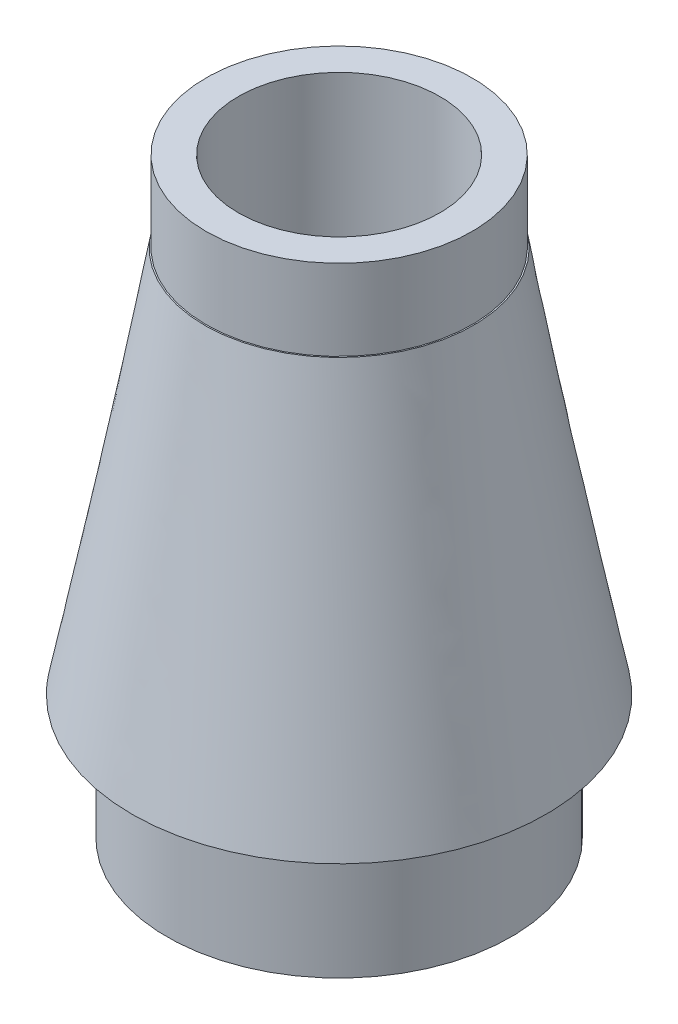
SolidWorks part; units mm, degrees
ref_plane "Front Plane" through (0, 0, 0) normal (0, 0, 1) x (1, 0, 0)
ref_plane "Top Plane" through (0, 0, 0) normal (0, 1, 0) x (1, 0, 0)
ref_plane "Right Plane" through (0, 0, 0) normal (1, 0, 0) x (0, 0, -1)
sketch "Sketch1" plane through (0, 0, 0) normal (0, 1, 0) x (1, 0, 0)
  circle A0 centre (0, 0) radius 3.2
  dimension "D1" = 6.4
ref_plane "Plane1" through (0, 2.3, 0) normal (0, 1, 0) x (-1, 0, 0)
sketch "Sketch2" plane through (0, 2.3, 0) normal (0, 1, 0) x (-1, 0, 0)
  circle A0 centre (0, 0) radius 3.85
  dimension "D1" = 7.7
ref_plane "Plane2" through (0, 9.5, 0) normal (0, 1, 0) x (-1, 0, 0)
sketch "Sketch3" plane through (0, 9.5, 0) normal (0, 1, 0) x (-1, 0, 0)
  circle A0 centre (0, 0) radius 2.5
  dimension "D1" = 5
ref_plane "Plane3" through (0, 11, 0) normal (0, 1, 0) x (-1, 0, 0)
sketch "Sketch4" plane through (0, 11, 0) normal (0, 1, 0) x (-1, 0, 0)
  circle A0 centre (0, 0) radius 2.475
  dimension "D1" = 4.95
loft "Loft4" add profiles "Sketch2", "Sketch3" connector at (3.5029, 2.3, -1.5975) connector at (2.4654, 9.5, -0.4143)
extrude "Boss-Extrude1" add sketch "Sketch4" against normal up to next
extrude "Boss-Extrude2" add sketch "Sketch1" along normal up to next
sketch "Sketch5" plane through (0, 0, 0) normal (0, -1, 0) x (1, 0, 0)
  circle A0 centre (0, 0) radius 2.475
  dimension "D1" = 4.95
extrude "Cut-Extrude1" cut sketch "Sketch5" against normal blind 4
sketch "Sketch6" plane through (0, 11, 0) normal (0, 1, 0) x (1, 0, 0)
  circle A0 centre (0, 0) radius 1.875
  circle A1 centre (0, 0) radius 2.475 construction
  dimension "D1" = 0.6
extrude "Cut-Extrude2" cut sketch "Sketch6" against normal up to next
